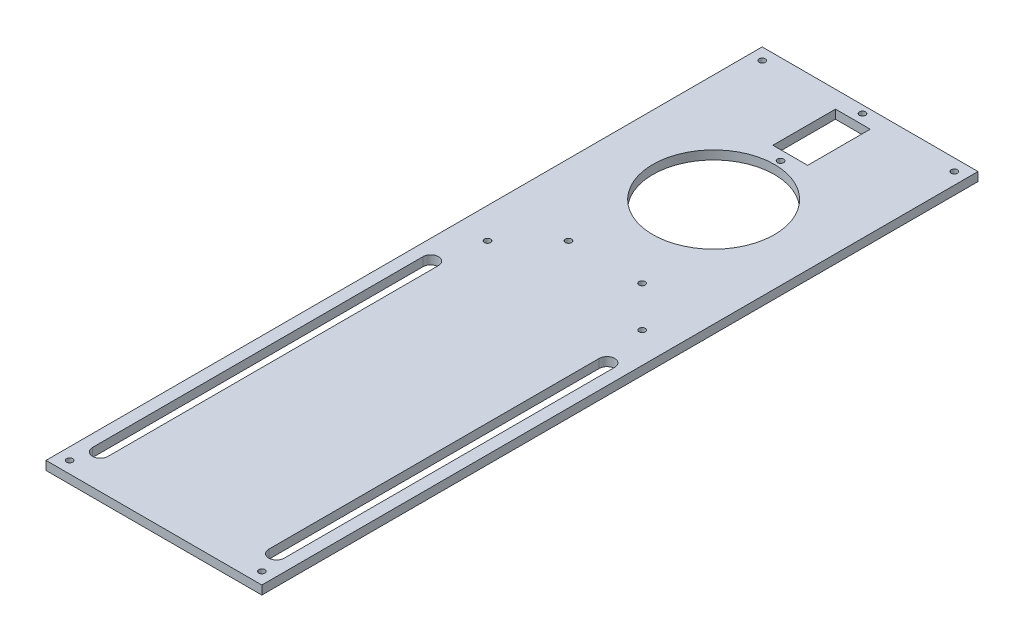
SolidWorks part; units mm, degrees
material "Brass"
ref_plane "Front Plane" through (0, 0, 0) normal (0, 0, 1) x (1, 0, 0)
ref_plane "Top Plane" through (0, 0, 0) normal (0, 1, 0) x (1, 0, 0)
ref_plane "Right Plane" through (0, 0, 0) normal (1, 0, 0) x (0, 0, -1)
sketch "Sketch2" plane through (0, 0, 0) normal (0, 0, 1) x (1, 0, 0)
  line L0 (-44.45, 0) -> (-44.45, -3.2004)
  line L1 (0, 0) -> (0, -3.2004) construction
  line L2 (-44.45, -3.2004) -> (34.3945, -3.2004)
  line L3 (34.3945, 0) -> (34.3945, -3.2004)
  line L4 (-44.45, 0) -> (34.3945, 0)
  dimension "D1" = 78.8445
  dimension "D2" = 3.2004
extrude "Boss-Extrude1" add sketch "Sketch2" along normal blind 261.62 contours L4 L3 L2 L0
sketch "Sketch3" plane through (0, -3.2004, 0) normal (0, -1, 0) x (1, 0, 0)
  line L0 (-44.45, 57.15) -> (34.3945, 57.15) construction
  line L1 (30.0765, 261.62) -> (30.0765, 257.302) construction
  line L2 (30.0765, 257.302) -> (34.3945, 257.302) construction
  line L3 (-44.45, 261.62) -> (34.3945, 261.62) construction
  line L4 (-5.0278, 57.15) -> (-5.0278, 0) construction
  line L5 (-44.45, 0) -> (34.3945, 0) construction
  line L6 (-40.0535, 128.3174) -> (-34.3859, 128.3174) construction
  line L7 (-40.0535, 128.3174) -> (-40.0535, 249.024)
  line L8 (-40.0535, 249.024) -> (-34.3859, 249.024) construction
  line L9 (-34.3859, 128.3174) -> (-34.3859, 249.024)
  line L10 (-37.2197, 261.62) -> (-37.2197, 251.8579) construction
  line L11 (-40.0535, 188.6707) -> (-44.45, 188.6707) construction
  line L12 (24.3303, 128.3174) -> (29.998, 128.3174) construction
  line L13 (24.3303, 128.3174) -> (24.3303, 249.024)
  line L14 (24.3303, 249.024) -> (29.998, 249.024) construction
  line L15 (29.998, 128.3174) -> (29.998, 249.024)
  line L16 (27.1642, 261.62) -> (27.1642, 251.8579) construction
  line L17 (34.3945, 188.6707) -> (29.998, 188.6707) construction
  line L18 (34.3945, 261.62) -> (34.3945, 0) construction
  line L19 (-44.45, 4.318) -> (-40.132, 4.318) construction
  line L20 (34.3945, 261.62) -> (34.3945, 0) construction
  line L21 (-44.45, 261.62) -> (-44.45, 0) construction
  line L22 (-44.45, 261.62) -> (-44.45, 0) construction
  line L23 (-40.132, 261.62) -> (-40.132, 257.302) construction
  line L24 (-44.45, 257.302) -> (-40.132, 257.302) construction
  line L25 (-44.45, 261.62) -> (34.3945, 261.62) construction
  line L26 (-40.132, 4.318) -> (-40.132, 0) construction
  line L27 (-44.45, 0) -> (34.3945, 0) construction
  line L28 (34.3945, 4.318) -> (30.0765, 4.318) construction
  line L29 (30.0765, 0) -> (30.0765, 4.318) construction
  line L30 (-11.3778, 29.1559) -> (-11.3778, 6.2959)
  line L31 (1.3222, 29.1559) -> (1.3222, 6.2959)
  line L32 (-11.3778, 6.2959) -> (1.3222, 6.2959)
  line L33 (-11.3778, 29.1559) -> (1.3222, 29.1559)
  line L34 (23.2109, 111.5162) -> (34.3945, 111.5162) construction
  line L35 (23.2109, 261.62) -> (23.2109, 111.5162) construction
  line L36 (8.4242, 96.7295) -> (23.2109, 111.5162) construction
  line L37 (-33.2664, 111.5162) -> (-44.45, 111.5162) construction
  line L38 (-33.2664, 111.5162) -> (-18.4797, 96.7295) construction
  circle A0 centre (-5.0278, 57.15) radius 22.225
  arc A1 (-40.0535, 249.024) -> (-34.3859, 249.024) centre (-37.2197, 249.024) cw
  arc A2 (-34.3859, 128.3174) -> (-40.0535, 128.3174) centre (-37.2197, 128.3174) cw
  arc A3 (24.3303, 249.024) -> (29.998, 249.024) centre (27.1642, 249.024) cw
  arc A4 (29.998, 128.3174) -> (24.3303, 128.3174) centre (27.1642, 128.3174) cw
  circle A5 centre (-40.132, 257.302) radius 1.1303
  circle A6 centre (30.0765, 257.302) radius 1.1303
  circle A7 centre (-40.132, 4.318) radius 1.1303
  circle A8 centre (30.0765, 4.318) radius 1.1303
  circle A9 centre (-5.0278, 32.6865) radius 1.1303
  circle A10 centre (-5.0278, 2.7653) radius 1.1303
  circle A11 centre (8.4242, 96.7295) radius 1.1303
  circle A12 centre (23.2109, 111.5162) radius 1.1303
  circle A13 centre (-33.2664, 111.5162) radius 1.1303
  circle A14 centre (-18.4797, 96.7295) radius 1.1303
  point P53 (-5.0278, 29.1559)
  point P58 (-5.0278, 29.1559)
  point P67 (-5.0278, 6.2959)
  dimension "D1" = 44.45
  dimension "D11" = 2.2606
  dimension "D15" = 2.2606
  dimension "D16" = 2.7653
  dimension "D18" = 3.5306
  dimension "D19" = 2.2606
  dimension "D2" = 57.15
  dimension "D3" = 120.7066
  dimension "D4" = 5.6676
  dimension "D5" = 9.7621
  dimension "D6" = 4.3965
  dimension "D7" = 120.7066
  dimension "D8" = 5.6676
  dimension "D9" = 9.7621
  dimension "D10" = 4.3965
  dimension "D12" = 4.318
  dimension "D13" = 22.86
  dimension "D14" = 12.7
  dimension "D17" = 3.5306
  dimension "D20" = 150.1038
  dimension "D21" = 11.1836
  dimension "D22" = 20.9115
  dimension "D23" = 45
  dimension "D24" = 45
extrude "Cut-Extrude1" cut sketch "Sketch3" against normal through all
sketch "Sketch4" plane through (0, 0, 261.62) normal (0, 0, 1) x (1, 0, 0)
  line L0 (-5.0278, 0) -> (-5.0278, -3.2004) construction
  line L1 (-44.45, 0) -> (34.3945, 0) construction
  line L2 (-44.45, -3.2004) -> (34.3945, -3.2004) construction
sketch "Sketch6" plane through (34.3945, 0, 0) normal (1, 0, 0) x (0, 0, -1)
  line L0 (-130.81, 0) -> (-130.81, -3.2004) construction
  line L3 (-261.62, -3.2004) -> (0, -3.2004) construction
  line L4 (-261.62, 0) -> (0, 0) construction
